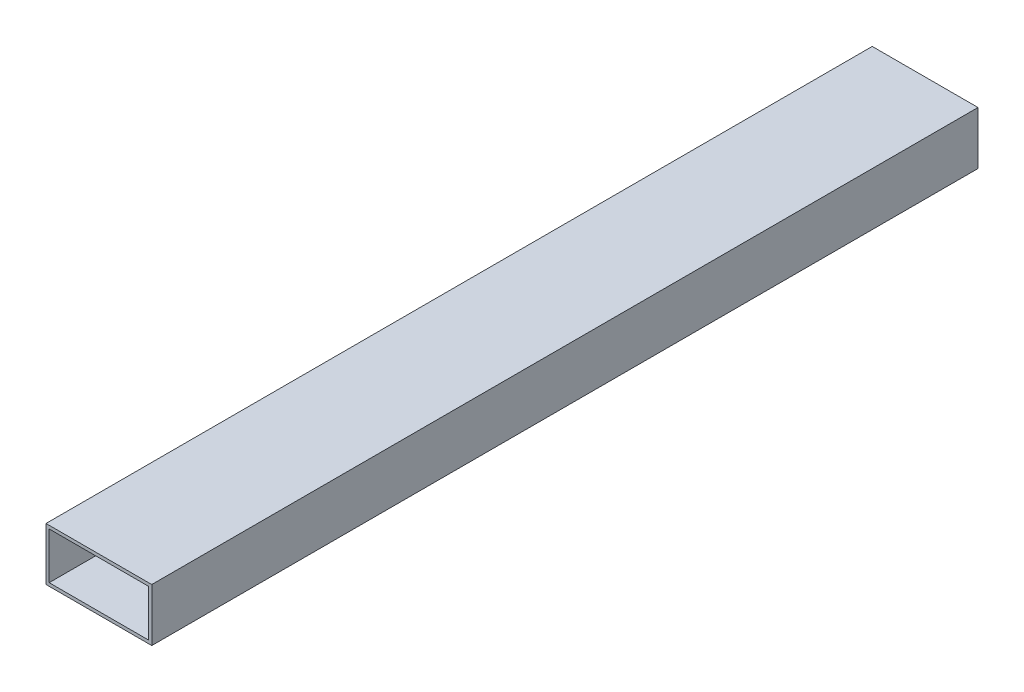
SolidWorks part; units mm, degrees
ref_plane "Front Plane" through (0, 0, 0) normal (0, 0, 1) x (1, 0, 0)
ref_plane "Top Plane" through (0, 0, 0) normal (0, 1, 0) x (1, 0, 0)
ref_plane "Right Plane" through (0, 0, 0) normal (1, 0, 0) x (0, 0, -1)
sketch "Sketch1" plane through (0, 0, 0) normal (0, 0, 1) x (1, 0, 0)
  line L1 (-81.2829, 22.6771) -> (-132.0829, 22.6771)
  line L2 (-81.2829, 22.6771) -> (-81.2829, 48.0771)
  line L3 (-81.2829, 48.0771) -> (-132.0829, 48.0771)
  line L4 (-132.0829, 22.6771) -> (-132.0829, 48.0771)
  dimension "D1" = 50.8
  dimension "D2" = 25.4
extrude "Extrude-Thin1" add sketch "Sketch1" along normal blind 396.875 thin thin type one direction reverse wall 1.524
